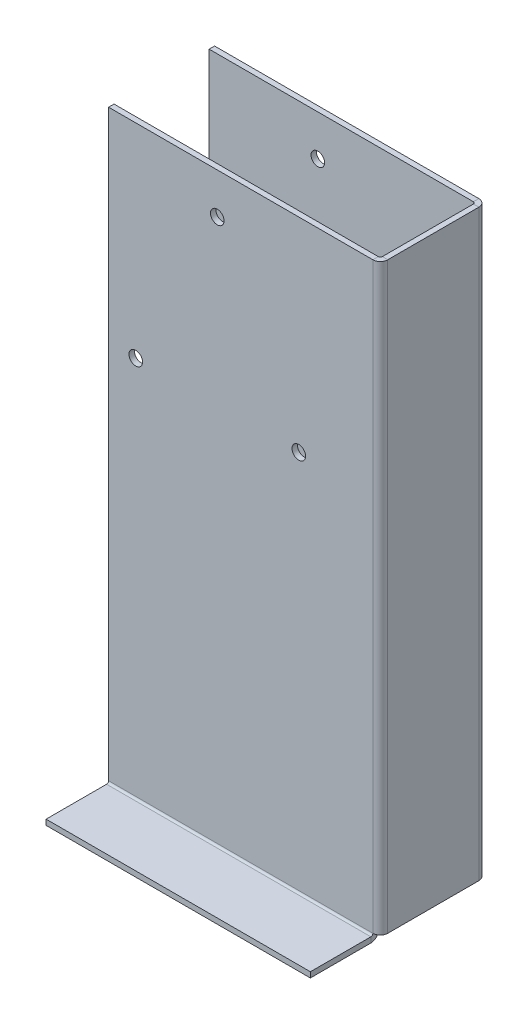
SolidWorks part; units mm, degrees
note: The reader was unsure of these and kept them because the rebuilt part matched: flange length of "Edge-Flange1", "Edge-Flange2", "Edge-Flange3".
ref_plane "Front Plane" through (0, 0, 0) normal (0, 0, 1) x (1, 0, 0)
ref_plane "Top Plane" through (0, 0, 0) normal (0, 1, 0) x (1, 0, 0)
ref_plane "Right Plane" through (0, 0, 0) normal (1, 0, 0) x (0, 0, -1)
sketch "Sketch1" plane through (0, 0, 0) normal (0, 0, 1) x (1, 0, 0)
  line L1 (0, 0) -> (100, 0)
  line L2 (0, 0) -> (0, 214.69)
  line L3 (0, 214.69) -> (100, 214.69)
  line L4 (100, 0) -> (100, 214.69)
  dimension "D1" = 214.69
  dimension "D2" = 100
base flange "Base-Flange1" sketch "Sketch1" thickness 2 reverse thickness direction no parameters "D1"=0.7366
edge flange "Edge-Flange1" sketch "Sketch8" flange angle 90 flange length 39 flange position material inside bend radius 0.7366 thickness 2 relief rectangular parameters "D6"=10
sketch "Sketch8" plane through (100, 0, -2) normal (-1, 0, 0) x (0, 1, 0)
  line L1 (214.69, 0) -> (0, 0) construction
  line L2 (0, 0) -> (0, 37)
  line L3 (0, 37) -> (214.69, 37)
  line L4 (214.69, 37) -> (214.69, 0)
  line L5 (214.69, 0) -> (0, 0)
bend "EdgeBend1" bend radius 0.7366 bend angle 90 parameters "D5"=1
edge flange "Edge-Flange2" sketch "Sketch11" flange angle 90 flange length 100 flange position material inside bend radius 0.7366 thickness 2 relief rectangular parameters "D6"=10
sketch "Sketch11" plane through (98, 0, -39) normal (0, 0, -1) x (0, -1, 0)
  line L0 (-214.69, 0) -> (0, 0) construction
  line L1 (-214.69, 0) -> (0, 0)
  line L2 (-214.69, 0) -> (-214.69, 98)
  line L3 (-214.69, 98) -> (0, 98)
  line L4 (0, 98) -> (0, 0)
bend "EdgeBend2" bend radius 0.7366 bend angle 90 parameters "D5"=2
edge flange "Edge-Flange3" sketch "Sketch16" flange profiles "Sketch16", "Sketch17" flange angle 90 flange length 25 flange position bend outside bend radius 0.7366 thickness 2 relief rectangular parameters "D6"=10, "D8"=1
sketch "Sketch16" plane through (0, 0, 0) normal (0, -1, 0) x (1, 0, 0)
  line L0 (0, 0) -> (97.2634, 0) construction
  line L1 (0, 0) -> (97.2634, 0)
  line L2 (0, 0) -> (0, 23)
  line L3 (0, 23) -> (97.2634, 23)
  line L4 (97.2634, 23) -> (97.2634, 0)
sketch "Sketch17" plane through (0, 0, -39) normal (0, -1, 0) x (-1, 0, 0)
  line L0 (-97.2634, 0) -> (0, 0) construction
  line L1 (-97.2634, 0) -> (0, 0)
  line L2 (-97.2634, 0) -> (-97.2634, 23)
  line L3 (-97.2634, 23) -> (0, 23)
  line L4 (0, 23) -> (0, 0)
bend "EdgeBend3" bend radius 0.7366 bend angle 90 parameters "D5"=3
bend "EdgeBend4" bend radius 0.7366 bend angle 90 parameters "D5"=4
sketch "Sketch18" plane through (0, -57.7366, -62) normal (0, 0, 1) x (1, 0, 0)
  line L1 (97.2634, 57.7366) -> (68.2634, 57.7366)
  line L2 (97.2634, 57.7366) -> (97.2634, 55)
  line L3 (97.2634, 55) -> (68.2634, 55)
  line L4 (68.2634, 57.7366) -> (68.2634, 55)
  line L6 (0, 57.7366) -> (27, 57.7366)
  line L7 (0, 57.7366) -> (0, 55)
  line L8 (0, 55) -> (27, 55)
  line L9 (27, 57.7366) -> (27, 55)
  line L13 (0, 55) -> (97.2634, 55) construction
  line L15 (97.2634, 57.7366) -> (0, 57.7366) construction
  line L16 (97.2634, 57) -> (97.2634, 55) construction
  line L17 (0, 57) -> (0, 55) construction
  dimension "D1" = 29
  dimension "D2" = 27
extrude "Cut-Extrude1" cut sketch "Sketch18" along normal up to surface (25 mm away) normal cut yes up to face at (48.6317, 107.345, -37)
sketch "Sketch19" plane through (0, 0, 0) normal (0, 0, 1) x (1, 0, 0)
  line L0 (97.2634, 214.69) -> (0, 214.69) construction
  line L1 (0, 214.69) -> (0, 0) construction
  circle A0 centre (40, 199.69) radius 2.5
  circle A1 centre (10, 139.69) radius 2.5
  circle A2 centre (70, 139.69) radius 2.5
  dimension "D1" = 5
  dimension "D2" = 15
  dimension "D3" = 40
  dimension "D5" = 30
  dimension "D6" = 60
  dimension "D4" = 60
extrude "Cut-Extrude2" cut sketch "Sketch19" against normal up to surface (39 mm away) normal cut yes up to face at (48.2984, 71.5633, -39)
sketch "Bend-Lines1" plane through (0, 0, 0) normal (0, 1, 0) x (1, 0, 0)
sketch "Bounding-Box1" plane through (0, 0, 0) normal (0, 1, 0) x (1, 0, 0)
sheet metal parameters "Sheet-Metal1" thickness 2 parameters "D1"=0.7366
flat pattern "Flat-Pattern1" [suppressed]
sketch "Bend-Lines2" plane through (0, 0, 0) normal (0, 1, 0) x (1, 0, 0)
sketch "Bounding-Box2" [suppressed] plane through (0, 0, 0) normal (0, 1, 0) x (1, 0, 0)
sheet metal parameters "Sheet-Metal2" thickness 2 parameters "D1"=0.7366
flat pattern "Flat-Pattern1" [suppressed]
sketch "Bend-Lines2" plane through (0, 0, 0) normal (0, 1, 0) x (1, 0, 0)
sketch "Bounding-Box2" [suppressed] plane through (0, 0, 0) normal (0, 1, 0) x (1, 0, 0)
bend of the flat pattern "Flatten-<EdgeBend1>1"
sheet metal parameters "Sheet-Metal3" thickness 2 parameters "D1"=0.7366
flat pattern "Flat-Pattern1" [suppressed]
sketch "Bend-Lines2" plane through (0, 0, 0) normal (0, 1, 0) x (1, 0, 0)
sketch "Bounding-Box2" [suppressed] plane through (0, 0, 0) normal (0, 1, 0) x (1, 0, 0)
bend of the flat pattern "Flatten-<EdgeBend1>1"
bend of the flat pattern "Flatten-<EdgeBend2>1"
sheet metal parameters "Sheet-Metal4" thickness 2 parameters "D1"=0.7366
flat pattern "Flat-Pattern1" [suppressed]
sketch "Bend-Lines2" plane through (0, 0, 0) normal (0, 1, 0) x (1, 0, 0)
sketch "Bounding-Box2" [suppressed] plane through (0, 0, 0) normal (0, 1, 0) x (1, 0, 0)
bend of the flat pattern "Flatten-<EdgeBend1>1"
bend of the flat pattern "Flatten-<EdgeBend2>1"
bend of the flat pattern "Flatten-<EdgeBend3>1"
bend of the flat pattern "Flatten-<EdgeBend4>1"
sheet metal parameters "Sheet-Metal5" thickness 2 parameters "D1"=0.7366
flat pattern "Flat-Pattern1" [suppressed]
sketch "Bend-Lines2" plane through (0, 0, 0) normal (0, 1, 0) x (1, 0, 0)
sketch "Bounding-Box2" [suppressed] plane through (0, 0, 0) normal (0, 1, 0) x (1, 0, 0)
bend of the flat pattern "Flatten-<EdgeBend1>1"
bend of the flat pattern "Flatten-<EdgeBend2>1"
bend of the flat pattern "Flatten-<EdgeBend3>1"
bend of the flat pattern "Flatten-<EdgeBend4>1"
sheet metal parameters "Sheet-Metal6" thickness 2 parameters "D1"=0.7366
flat pattern "Flat-Pattern1" [suppressed]
sketch "Bend-Lines2" plane through (0, 0, 0) normal (0, 1, 0) x (1, 0, 0)
sketch "Bounding-Box2" [suppressed] plane through (0, 0, 0) normal (0, 1, 0) x (1, 0, 0)
bend of the flat pattern "Flatten-<EdgeBend1>1"
bend of the flat pattern "Flatten-<EdgeBend2>1"
bend of the flat pattern "Flatten-<EdgeBend3>1"
bend of the flat pattern "Flatten-<EdgeBend4>1"
